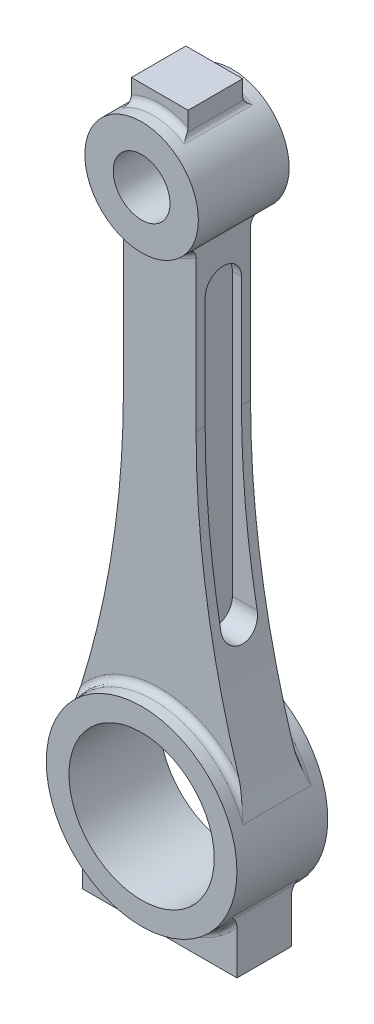
SolidWorks part; units mm, degrees
ref_plane "Front Plane" through (0, 0, 0) normal (0, 0, 1) x (1, 0, 0)
ref_plane "Top Plane" through (0, 0, 0) normal (0, 1, 0) x (1, 0, 0)
ref_plane "Right Plane" through (0, 0, 0) normal (1, 0, 0) x (0, 0, -1)
sketch "Sketch1" plane through (0, 0, 0) normal (0, 0, 1) x (1, 0, 0)
  circle A0 centre (0, 0) radius 16
  circle A1 centre (0, 0) radius 21
  circle A2 centre (0, 120) radius 12.5
  circle A3 centre (0, 120) radius 6.25
  dimension "D1" = 42
  dimension "D2" = 32
  dimension "D3" = 25
  dimension "D4" = 12.5
  dimension "D5" = 120
extrude "Boss-Extrude1" add sketch "Sketch1" along normal mid plane 20
sketch "Sketch2" plane through (0, 0, 0) normal (0, 0, 1) x (1, 0, 0)
  line L0 (8, 110.3953) -> (8, 75.3953)
  line L1 (0, 120) -> (0, 86.6679) construction
  line L2 (-8, 110.3953) -> (-8, 75.3953)
  circle A0 centre (0, 120) radius 12.5 construction
  circle A1 centre (0, 0) radius 21 construction
  circle A2 centre (0, 120) radius 12.5
  circle A3 centre (0, 0) radius 21
  arc A4 (8, 75.3953) -> (19.7874, 7.0327) centre (212.1328, 75.3953) ccw
  arc A5 (-8, 75.3953) -> (-19.7874, 7.0327) centre (-212.1328, 75.3953) cw
  dimension "D1" = 8
  dimension "D2" = 35
extrude "Boss-Extrude2" add sketch "Sketch2" along normal mid plane 12 contours L2 A5 A3 A4 L0 A2 region at (0, 57.8448, 0)
sketch "Sketch3" plane through (0, 0, 0) normal (0, 0, 1) x (1, 0, 0)
  line L0 (0, 149.3562) -> (0, -30.2563) construction
  line L1 (-6.25, 135.8253) -> (-6.25, 130.8253)
  line L2 (6.25, 135.8253) -> (6.25, 130.8253)
  line L3 (-6.25, 135.8253) -> (6.25, 135.8253)
  line L4 (-17, -24.3288) -> (-17, -12.3288)
  line L5 (17, -24.3288) -> (17, -12.3288)
  line L6 (-17, -24.3288) -> (17, -24.3288)
  circle A0 centre (0, 120) radius 12.5 construction
  arc A1 (0, 107.5) -> (-6.25, 130.8253) centre (0, 120) ccw
  circle A2 centre (0, 0) radius 21 construction
  arc A3 (-17, -12.3288) -> (17, -12.3288) centre (0, 0) ccw
  dimension "D1" = 5
  dimension "D2" = 12.5
  dimension "D3" = 12
  dimension "D4" = 34
extrude "Boss-Extrude3" add sketch "Sketch3" along normal mid plane 12 contours A3 L0 L6 L5 | L0 A3 L4 L6 | L3 L0 A1 L2 | L0 L3 L1 A1 region at (3.3472, 133.8599, 0) region at (-3.3472, 133.8599, 0) region at (10.4494, -20.8498, 0) region at (-10.4494, -20.8498, 0)
fillet "Fillet1" radius 1.5 12 edges at (17, -12.3288, 0) (0, -21, -6) (-17, -12.3288, 0) (0, -21, 6) (0, 107.5, -6) (0, 21, -6) (0, 21, 6) (0, 107.5, 6) (-6.25, 130.8253, 0) (0, 132.5, -6) (0, 132.5, 6) (6.25, 130.8253, 0)
ref_plane "Plane1" through (6, 0, 0) normal (1, 0, 0) x (0, 0, -1)
sketch "Sketch4" plane through (6, 0, 0) normal (1, 0, 0) x (0, 0, -1)
  line L0 (0, 100) -> (0, 38) construction
  line L1 (4, 100) -> (4, 38)
  line L2 (-4, 100) -> (-4, 38)
  line L3 (-10, 120) -> (10, 120) construction
  line L4 (-10, 132.5) -> (-10, 107.5) construction
  line L5 (10, 107.5) -> (10, 132.5) construction
  arc A0 (4, 100) -> (-4, 100) centre (0, 100) ccw
  arc A1 (-4, 38) -> (4, 38) centre (0, 38) ccw
  point P3 (0, 69)
  dimension "D1" = 4
  dimension "D2" = 62
  dimension "D3" = 20
extrude "Cut-Extrude1" cut sketch "Sketch4" along normal blind 75
mirror "Mirror2" about plane through (0, 0, 0) normal (1, 0, 0) of "Cut-Extrude1"
